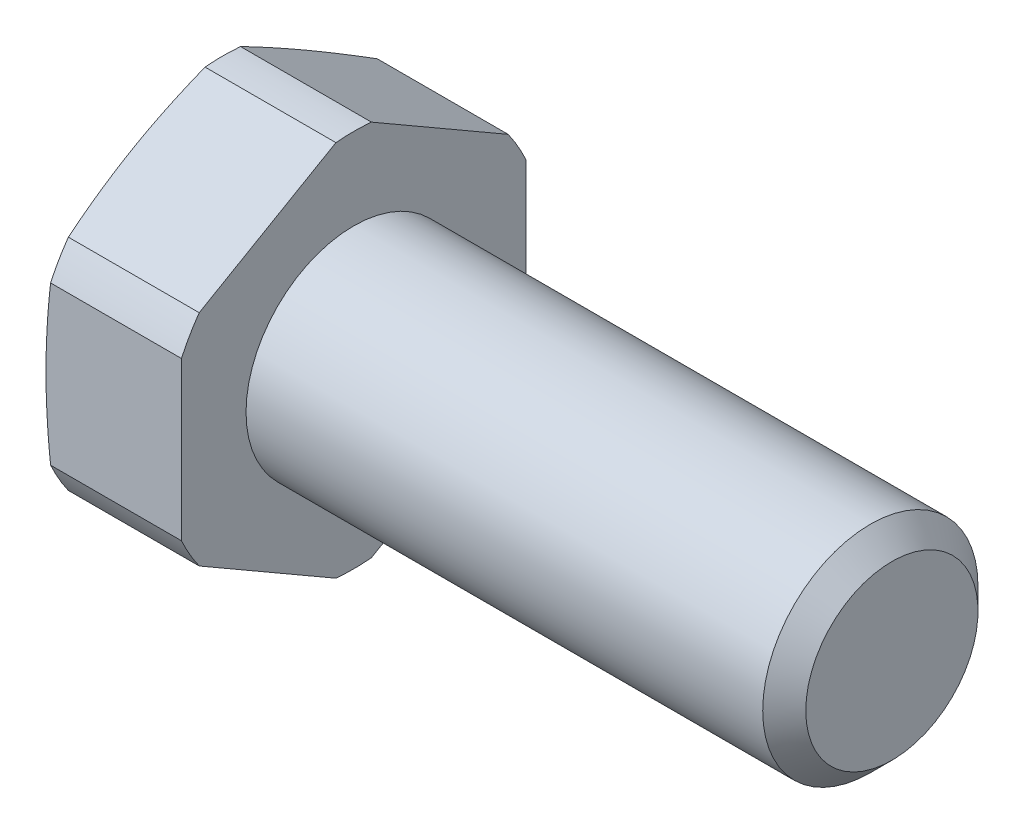
SolidWorks part; units mm, degrees
ref_plane "Спереди" through (0, 0, 0) normal (0, 0, 1) x (1, 0, 0)
ref_plane "Сверху" through (0, 0, 0) normal (0, 1, 0) x (1, 0, 0)
ref_plane "Справа" through (0, 0, 0) normal (1, 0, 0) x (0, 0, -1)
sketch "Эскиз1" plane through (0, 0, 0) normal (0, 0, 1) x (1, 0, 0)
  line L0 (-1000, 0) -> (49000, 0) construction
  line L1 (-6.4, 0) -> (-6.4, 7.6)
  line L2 (-6.4, 7.6) -> (-6.0785, 8.8)
  line L3 (-6.0785, 8.8) -> (0, 8.8)
  line L4 (0, 8.8) -> (0, 5)
  line L5 (0, 5) -> (24, 5)
  line L6 (25, 4) -> (25, 0)
  line L7 (25, 5) -> (25.75, 6.299) construction
  line L8 (25.75, 6.299) -> (26.5, 5) construction
  line L9 (26.5, 5) -> (25, 5) construction
  line L10 (25.75, 6.299) -> (25.75, 5) construction
  line L11 (25.75, 6.299) -> (0.75, 6.299) construction
  line L12 (24, 5) -> (25, 4)
  line L13 (25, 5) -> (24.5, 4.5) construction
  line L14 (-6.4, 7.6) -> (-22.4, 7.6) construction
  line L15 (-6.4, 0) -> (25, 0)
  dimension "D1" = 1
  dimension "D2" = 15
revolve "Повернуть1" add sketch "Эскиз1" angle 360 about L0
cosmetic thread "Условное изображение резьбы1" parameters "D1"=25, "D2"=7.4019
sketch "Эскиз2" plane through (-6.4, 0, 0) normal (-1, 0, 0) x (0, 0, 1)
  line L1 (0, 9.2376) -> (-8, 4.6188)
  line L2 (-8, 4.6188) -> (-8, -4.6188)
  line L3 (-8, -4.6188) -> (0, -9.2376)
  line L4 (0, -9.2376) -> (8, -4.6188)
  line L5 (8, -4.6188) -> (8, 4.6188)
  line L6 (8, 4.6188) -> (0, 9.2376)
  circle A0 centre (0, 0) radius 8 construction
  dimension "D1" = 16
extrude "Вырез-Вытянуть1" cut sketch "Эскиз2" against normal up to surface (31.4 mm away) flip side to cut up to face at (25, 0, 4)
other "PropertyManager"
equation "\"D1@Эскиз1\"=\"_d_@Эскиз1\"/10"
equation "\"D@Эскиз1\"=\"S_@Эскиз1\"*0.95"
equation "\"D1@Эскиз2\"=\"S_@Эскиз1\""
equation "\"D1@Условное изображение резьбы1\"=\"b_@Эскиз1\""
equation "\"D2@Условное изображение резьбы1\"=\"_d_@Эскиз1\"-\"dr@Эскиз1\"*2"
